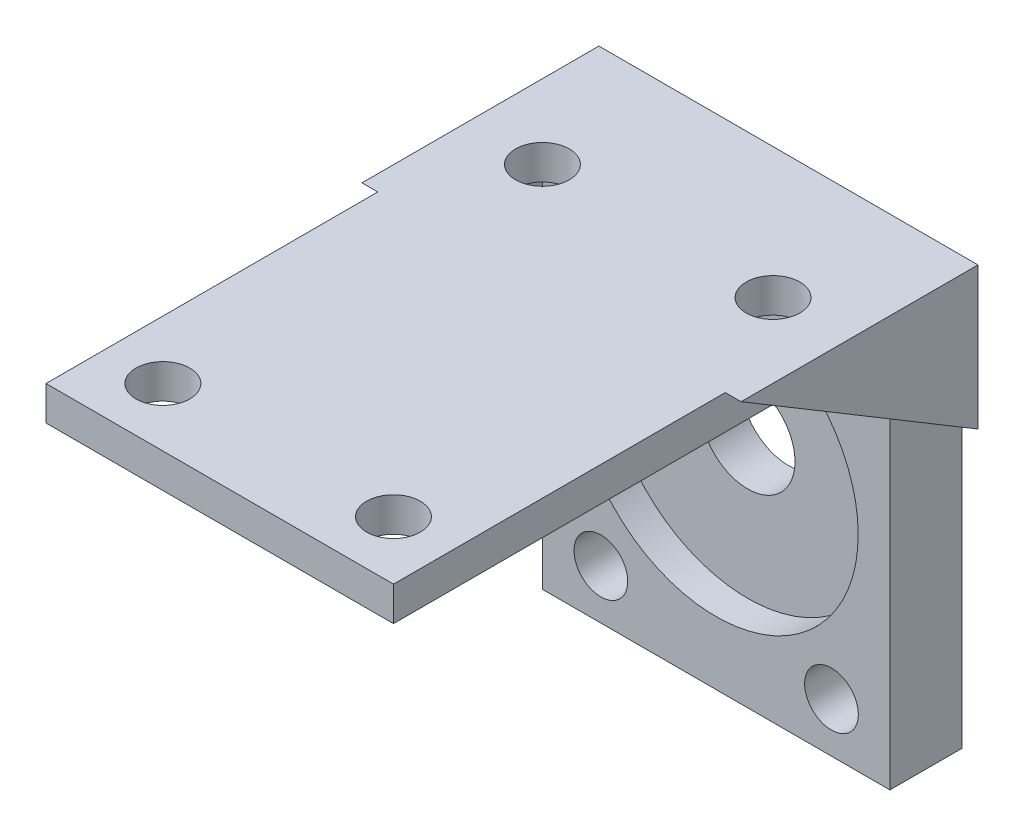
SolidWorks part; units mm, degrees
ref_plane "Front Plane" through (0, 0, 0) normal (0, 0, 1) x (1, 0, 0)
ref_plane "Top Plane" through (0, 0, 0) normal (0, 1, 0) x (1, 0, 0)
ref_plane "Right Plane" through (0, 0, 0) normal (1, 0, 0) x (0, 0, -1)
sketch "Sketch1" plane through (0, 0, 0) normal (0, 0, 1) x (1, 0, 0)
  line L1 (0, 0) -> (22, 0)
  line L2 (0, 0) -> (0, 27)
  line L3 (0, 27) -> (22, 27)
  line L4 (22, 0) -> (22, 27)
  dimension "D1" = 27
  dimension "D2" = 22
extrude "Boss-Extrude1" add sketch "Sketch1" along normal blind 4.577 contours L4 L3 L2 L1
sketch "Sketch2" plane through (0, 0, 4.577) normal (0, 0, 1) x (1, 0, 0)
  line L0 (22, 0) -> (22, 27) construction
  line L1 (0, 27) -> (22, 27)
  line L2 (0, 27) -> (0, 24.833)
  line L3 (0, 24.833) -> (22, 24.833)
  line L4 (22, 27) -> (22, 24.833)
  dimension "D1" = 22
  dimension "D2" = 2.167
extrude "Boss-Extrude2" add sketch "Sketch2" along normal blind 31.43 contours L3 L4 L1 L2
sketch "Sketch5" plane through (0, 24.833, 0) normal (0, -1, 0) x (1, 0, 0)
  circle A0 centre (3.7, 8.277) radius 1.7
  dimension "D3" = 3.4
extrude "Cut-Extrude1" cut sketch "Sketch5" against normal through all
sketch "Sketch6" plane through (0, 24.833, 0) normal (0, -1, 0) x (1, 0, 0)
  circle A0 centre (18.3, 8.277) radius 1.7
  dimension "D1" = 3.4
extrude "Cut-Extrude2" cut sketch "Sketch6" against normal through all
sketch "Sketch7" plane through (0, 24.833, 0) normal (0, -1, 0) x (1, 0, 0)
  circle A0 centre (3.7, 32.307) radius 1.7
  dimension "D3" = 3.4
extrude "Cut-Extrude3" cut sketch "Sketch7" against normal through all
sketch "Sketch8" plane through (0, 24.833, 0) normal (0, -1, 0) x (1, 0, 0)
  circle A0 centre (18.3, 32.307) radius 1.7
  dimension "D3" = 3.4
extrude "Cut-Extrude4" cut sketch "Sketch8" against normal through all
sketch "Sketch10" plane through (0, 0, 4.577) normal (0, 0, 1) x (1, 0, 0)
  circle A0 centre (10.9914, 13) radius 9
  circle A1 centre (3.7, 21.7) radius 1.7
  circle A2 centre (18.3, 21.7) radius 1.7
  circle A3 centre (3.7, 3.133) radius 1.7
  circle A4 centre (18.3, 3.133) radius 1.7
  circle A5 centre (10.9914, 13) radius 3
  dimension "D1" = 18
  dimension "D2" = 3.4
  dimension "D6" = 3.4
  dimension "D3" = 3.4
  dimension "D4" = 3.4
  dimension "D5" = 6
sketch "Sketch12" plane through (22, 0, 0) normal (1, 0, 0) x (0, 0, -1)
  line L0 (0, 27) -> (-15, 27)
  line L1 (-36.007, 27) -> (0, 27) construction
  line L2 (-15, 27) -> (0, 18)
  line L3 (0, 0) -> (0, 27) construction
  line L4 (0, 18) -> (0, 27)
  line L5 (-36.007, 24.833) -> (-4.577, 24.833) construction
  line L6 (-4.577, 0) -> (-4.577, 24.833) construction
  dimension "D1" = 15
  dimension "D2" = 9
  dimension "D3" = 90
extrude "Boss-Extrude6" add sketch "Sketch12" along normal blind 1 contours L2 L4 L0
sketch "Sketch13" plane through (0, 0, 0) normal (-1, 0, 0) x (0, 0, 1)
  line L0 (0, 27) -> (0, 18)
  line L1 (0, 0) -> (0, 27) construction
  line L2 (0, 18) -> (15, 27)
  line L3 (36.007, 27) -> (0, 27) construction
  line L4 (15, 27) -> (0, 27)
  line L5 (4.577, 0) -> (4.577, 24.833) construction
  line L6 (36.007, 24.833) -> (4.577, 24.833) construction
  dimension "D1" = 15
  dimension "D2" = 9
  dimension "D3" = 90
extrude "Boss-Extrude7" add sketch "Sketch13" along normal blind 1 contours L2 L4 L0
extrude "Cut-Extrude6" cut sketch "Sketch10" against normal through all contours A2
extrude "Cut-Extrude7" cut sketch "Sketch10<7>" against normal blind 10 contours A1
sketch "Sketch10<7>" plane through (0, 0, 4.577) normal (0, 0, 1) x (1, 0, 0) same geometry as "Sketch10"
extrude "Cut-Extrude8" cut sketch "Sketch10<8>" against normal blind 10 contours A4
sketch "Sketch10<8>" plane through (0, 0, 4.577) normal (0, 0, 1) x (1, 0, 0) same geometry as "Sketch10"
extrude "Cut-Extrude9" cut sketch "Sketch10<9>" against normal blind 10 contours A3
sketch "Sketch10<9>" plane through (0, 0, 4.577) normal (0, 0, 1) x (1, 0, 0) same geometry as "Sketch10"
extrude "Cut-Extrude10" cut sketch "Sketch10<10>" against normal blind 2 contours A0
sketch "Sketch10<10>" plane through (0, 0, 4.577) normal (0, 0, 1) x (1, 0, 0) same geometry as "Sketch10"
extrude "Cut-Extrude11" cut sketch "Sketch10<12>" against normal through all contours A5
sketch "Sketch10<12>" plane through (0, 0, 4.577) normal (0, 0, 1) x (1, 0, 0) same geometry as "Sketch10"
equation "\"Ys\"= 26 * 10 ^ 6"
equation "\"E\"= 3500 * 10 ^ 6"
equation "\"L1\"= 27mm"
equation "\"Dmax\"= 0.30mm"
equation "\"P(force)\"= 200"
equation "\"Safety Factor\"= 3"
equation "\"L2\"= 31.43mm"
equation "\"H1\"= 22mm"
equation "\"H2\"= 22mm"
equation "\"B1\"= 4.577mm"
equation "\"B2\"= 2.167mm"
equation "\"D1@Sketch1\"=\"L1\""
equation "\"D2@Sketch1\"=\"H1\""
equation "\"D1@Boss-Extrude1\"=\"B1\""
equation "\"D2@Sketch2\"=\"B2\""
equation "\"D1@Boss-Extrude2\"=\"L2\""
